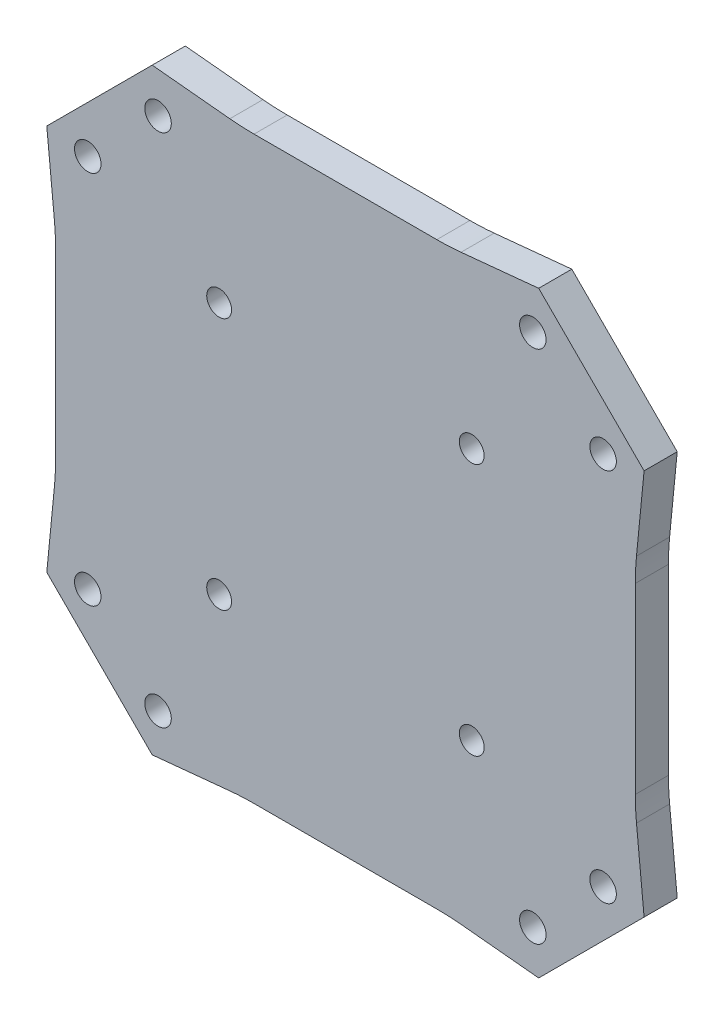
SolidWorks part; units mm, degrees
ref_plane "Front Plane" through (0, 0, 0) normal (0, 0, 1) x (1, 0, 0)
ref_plane "Top Plane" through (0, 0, 0) normal (0, 1, 0) x (1, 0, 0)
ref_plane "Right Plane" through (0, 0, 0) normal (1, 0, 0) x (0, 0, -1)
sketch "Sketch1" plane through (0, 0, 0) normal (0, 0, 1) x (1, 0, 0)
  line L0 (0, 0) -> (0, 35) construction
  line L1 (35, -35) -> (-35, -35) construction
  line L2 (35, -35) -> (35, 35) construction
  line L3 (35, 35) -> (-35, 35) construction
  line L4 (-35, -35) -> (-35, 35) construction
  line L5 (35, -35) -> (-35, 35) construction
  line L6 (35, 35) -> (-35, -35) construction
  line L7 (12.5, 35) -> (-12.5, 35)
  line L8 (35, -12.5) -> (35, 12.5)
  line L9 (-12.5, -35) -> (12.5, -35)
  line L10 (-35, 12.5) -> (-35, -12.5)
  line L11 (36.0624, 23.3345) -> (23.3345, 36.0624)
  line L12 (40.237, 13.5031) -> (13.5031, 40.237) construction
  line L13 (12.5, 35) -> (23.3345, 36.0624)
  line L14 (35, 12.5) -> (36.0624, 23.3345)
  line L15 (35, -12.5) -> (36.0624, -23.3345)
  line L16 (23.3345, -36.0624) -> (36.0624, -23.3345)
  line L17 (12.5, -35) -> (23.3345, -36.0624)
  line L18 (-12.5, -35) -> (-23.3345, -36.0624)
  line L19 (-36.0624, -23.3345) -> (-23.3345, -36.0624)
  line L20 (-35, -12.5) -> (-36.0624, -23.3345)
  line L21 (-35, 12.5) -> (-36.0624, 23.3345)
  line L22 (-23.3345, 36.0624) -> (-36.0624, 23.3345)
  line L23 (-12.5, 35) -> (-23.3345, 36.0624)
  circle A0 centre (31.1127, 22.6274) radius 1.6
  circle A1 centre (22.6274, 31.1127) radius 1.6
  circle A2 centre (22.6274, -31.1127) radius 1.6
  circle A3 centre (31.1127, -22.6274) radius 1.6
  circle A4 centre (-31.1127, -22.6274) radius 1.6
  circle A5 centre (-22.6274, -31.1127) radius 1.6
  circle A6 centre (-22.6274, 31.1127) radius 1.6
  circle A7 centre (-31.1127, 22.6274) radius 1.6
  point P0 (0, 0)
  point P11 (0, 35)
  point P20 (0, 0)
  point P22 (26.8701, 26.8701)
  point P24 (29.6985, 29.6985)
  point P25 (35, 35)
  point P26 (26.8701, 26.8701)
  point P57 (0, 0)
  dimension "D9" = 3.2
  dimension "D11" = 6
  dimension "D12" = 3.2
  dimension "D1" = 70
  dimension "D2" = 70
  dimension "D3" = 12.5
  dimension "D4" = 4
  dimension "D5" = 18
  dimension "D6" = 10.8865
  dimension "D7" = 10.8345
  dimension "D8" = 4
  dimension "D10" = 6
  dimension "D13" = 4
extrude "Boss-Extrude1" add sketch "Sketch1" along normal blind 4
sketch3d "3DSketch1"
  line L0 (0, 0, 0) -> (0, 37.4672, 0) construction
  line L1 (0, 0, 0) -> (38.0204, 0, 0) construction
  line L2 (0, 0, 0) -> (0, -36.1596, 0) construction
  line L3 (0, 0, 0) -> (-43.653, 0, 0) construction
  line L4 (-17.5226, 30.2505, 0.3337) -> (17.5226, 30.2505, 0.3337)
  line L5 (17.5226, 30.2505, 0.3337) -> (30.2505, 17.5226, 0.3337)
  line L6 (30.2505, 17.5226, 0.3337) -> (30.2505, -17.5226, 0.3337)
  line L7 (30.2505, -17.5226, 0.3337) -> (17.5226, -30.2505, 0.3337)
  line L8 (17.5226, -30.2505, 0.3337) -> (-17.5226, -30.2505, 0.3337)
  line L9 (-17.5226, -30.2505, 0.3337) -> (-30.2505, -17.5226, 0.3337)
  line L10 (-30.2505, -17.5226, 0.3337) -> (-30.2505, 17.5226, 0.3337)
  line L11 (-30.2505, 17.5226, 0.3337) -> (-17.5226, 30.2505, 0.3337)
  line L12 (-35, 12.5, 4) -> (-35, -12.5, 4) construction
  line L14 (-36.0624, -23.3345, 4) -> (-23.3345, -36.0624, 4) construction
  line L15 (-12.5, -35, 4) -> (12.5, -35, 4) construction
  line L16 (23.3345, -36.0624, 4) -> (36.0624, -23.3345, 4) construction
  line L18 (36.0624, 23.3345, 4) -> (23.3345, 36.0624, 4) construction
  line L19 (-23.3345, 36.0624, 4) -> (-36.0624, 23.3345, 4) construction
  dimension "D1" = 6
  dimension "D2" = 9
  dimension "D5" = 9
  dimension "D3" = 9
  dimension "D4" = 6
extrude "Cut-Extrude7" cut sketch "3DSketch1" along direction (0, 0, 1) on the side against the normal mid plane 2 contours L5 L6 L7 L8 L9 L10 L11 L4
sketch "Sketch7" plane through (0, 0, 1.3337) normal (0, 0, -1) x (-1, 0, 0)
  line L0 (0, 0) -> (0, 30.2505) construction
  line L1 (17.5226, 30.2505) -> (-17.5226, 30.2505) construction
  line L2 (0, 0) -> (-30.2505, 0) construction
  line L3 (-30.2505, 17.5226) -> (-30.2505, -17.5226) construction
  line L4 (-15, -4.5066) -> (-15, 4.5066)
  line L5 (-25.442, 13.8895) -> (-16.1915, 6.9002)
  line L6 (-16.1915, -6.9002) -> (-25.442, -13.8895)
  line L7 (-30.2505, -11.4959) -> (-30.2505, 11.4959)
  line L8 (13.8895, 25.442) -> (6.9002, 16.1915)
  line L9 (-4.5066, 15) -> (4.5066, 15)
  line L10 (-6.9002, 16.1915) -> (-13.8895, 25.442)
  line L11 (-11.4959, 30.2505) -> (11.4959, 30.2505)
  line L12 (25.442, -13.8895) -> (16.1915, -6.9002)
  line L13 (15, 4.5066) -> (15, -4.5066)
  line L14 (16.1915, 6.9002) -> (25.442, 13.8895)
  line L15 (30.2505, 11.4959) -> (30.2505, -11.4959)
  line L16 (-13.8895, -25.442) -> (-6.9002, -16.1915)
  line L17 (4.5066, -15) -> (-4.5066, -15)
  line L18 (6.9002, -16.1915) -> (13.8895, -25.442)
  line L19 (11.4959, -30.2505) -> (-11.4959, -30.2505)
  arc A0 (-30.2505, -11.4959) -> (-25.442, -13.8895) centre (-27.2505, -11.4959) ccw
  arc A1 (-15, 4.5066) -> (-16.1915, 6.9002) centre (-18, 4.5066) ccw
  arc A2 (-16.1915, -6.9002) -> (-15, -4.5066) centre (-18, -4.5066) ccw
  arc A3 (-25.442, 13.8895) -> (-30.2505, 11.4959) centre (-27.2505, 11.4959) ccw
  arc A4 (-6.9002, 16.1915) -> (-4.5066, 15) centre (-4.5066, 18) ccw
  arc A5 (4.5066, 15) -> (6.9002, 16.1915) centre (4.5066, 18) ccw
  arc A6 (-11.4959, 30.2505) -> (-13.8895, 25.442) centre (-11.4959, 27.2505) ccw
  arc A7 (13.8895, 25.442) -> (11.4959, 30.2505) centre (11.4959, 27.2505) ccw
  arc A8 (16.1915, 6.9002) -> (15, 4.5066) centre (18, 4.5066) ccw
  arc A9 (15, -4.5066) -> (16.1915, -6.9002) centre (18, -4.5066) ccw
  arc A10 (30.2505, 11.4959) -> (25.442, 13.8895) centre (27.2505, 11.4959) ccw
  arc A11 (25.442, -13.8895) -> (30.2505, -11.4959) centre (27.2505, -11.4959) ccw
  arc A12 (6.9002, -16.1915) -> (4.5066, -15) centre (4.5066, -18) ccw
  arc A13 (-4.5066, -15) -> (-6.9002, -16.1915) centre (-4.5066, -18) ccw
  arc A14 (11.4959, -30.2505) -> (13.8895, -25.442) centre (11.4959, -27.2505) ccw
  arc A15 (-13.8895, -25.442) -> (-11.4959, -30.2505) centre (-11.4959, -27.2505) ccw
  point P11 (-15, 0)
  point P17 (-30.2505, -17.5226)
  point P20 (-15, 6)
  point P25 (-30.2505, 17.5226)
  point P65 (0, 0)
  dimension "D3" = 3
  dimension "D1" = 6
  dimension "D2" = 15
  dimension "D4" = 4
extrude "Cut-Extrude8" cut sketch "Sketch7" against normal blind 1.5
sketch "Sketch8" plane through (0, 0, 1.3337) normal (0, 0, -1) x (-1, 0, 0)
  line L1 (0, 0) -> (15.25, 0) construction
  line L2 (0, 0) -> (0, 15.25) construction
  line L3 (0, 15.25) -> (15.25, 15.25) construction
  line L4 (15.25, 0) -> (15.25, 15.25) construction
  circle A0 centre (15.25, 15.25) radius 4
  dimension "D2" = 8
  dimension "D1" = 15.25
extrude "Boss-Extrude5" add sketch "Sketch8" along normal blind 1.5
sketch "Sketch13" plane through (0, 0, -0.1663) normal (0, 0, -1) x (-1, 0, 0)
  circle A0 centre (15.25, 15.25) radius 1.5
  dimension "D1" = 3
extrude "Cut-Extrude12" cut sketch "Sketch13" against normal blind 17.5
ref_axis "Axis1" through (0, 0, -0.3747) along (0, 0, 1)
pattern_circular "CirPattern2" count 4 over 360 about axis through (0, 0, -0.3747) along (0, 0, 1) of "Cut-Extrude12", "Boss-Extrude5"
fillet "Fillet2" radius 2 4 edges at (-15.25, -19.25, 1.3337) (-19.25, 15.25, 1.3337) (15.25, 19.25, 1.3337) (19.25, -15.25, 1.3337)
fillet "Fillet3" radius 30 8 edges at (35, -12.5, 2) (35, 12.5, 2) (12.5, 35, 2) (-12.5, 35, 2) (-35, 12.5, 2) (-35, -12.5, 2) (-12.5, -35, 2) (12.5, -35, 2)
